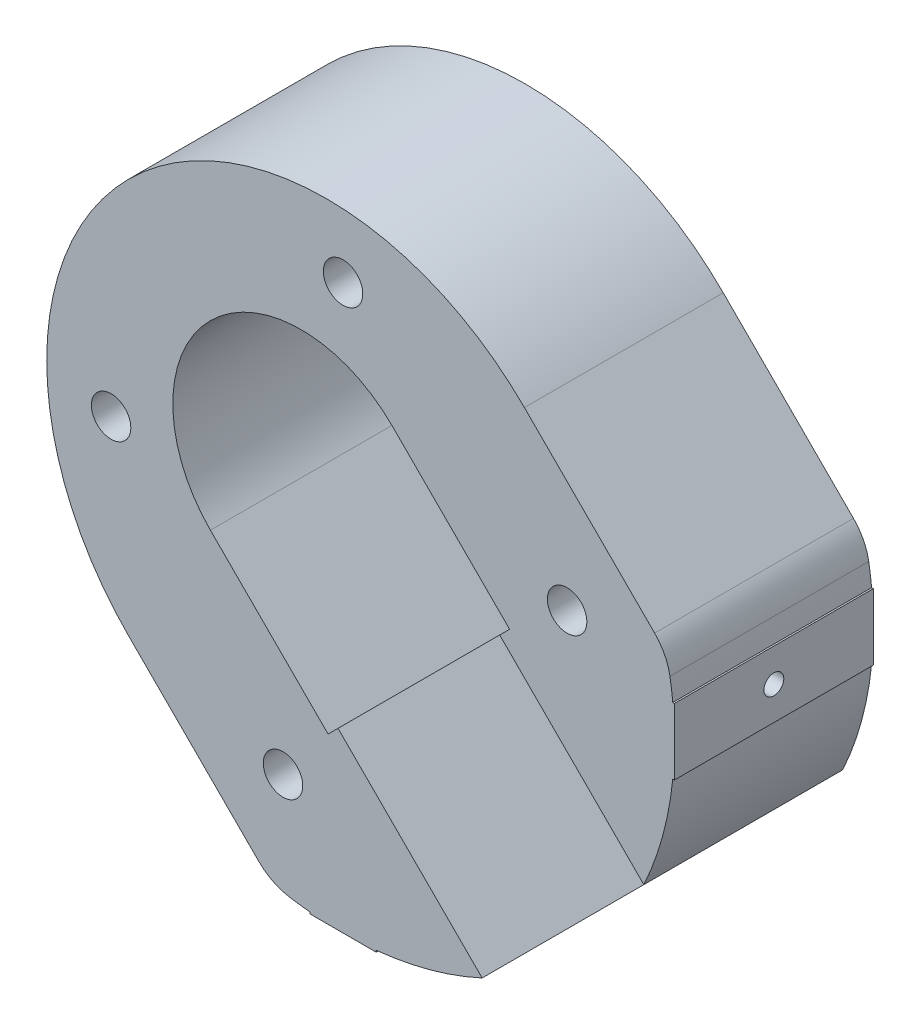
SolidWorks part; units mm, degrees
ref_plane "Front Plane" through (0, 0, 0) normal (0, 0, 1) x (1, 0, 0)
ref_plane "Top Plane" through (0, 0, 0) normal (0, 1, 0) x (1, 0, 0)
ref_plane "Right Plane" through (0, 0, 0) normal (1, 0, 0) x (0, 0, -1)
ref_axis "Z" through (0, 0, 33.5996) along (0, 0, -1)
ref_axis "X" through (56.0652, 0, 0) along (-1, 0, 0)
ref_axis "Y" through (0, -54.2845, 0) along (0, 1, 0)
sketch "Sketch1" plane through (0, 0, 0) normal (0, 0, 1) x (1, 0, 0)
  line L0 (5, -50) -> (-5, -50)
  line L1 (50, 5) -> (50, -5)
  line L2 (56.0652, 0) -> (-1.1166, 0) construction
  line L3 (0, -54.2845) -> (0, 1.1167) construction
  line L4 (61.712, 0) -> (50, 0) construction
  line L5 (0, -50) -> (0, -57.4075) construction
  line L6 (50, -5) -> (49.7494, -5)
  line L7 (5, -49.7494) -> (5, -50)
  line L10 (65.572, -65.572) -> (0, 0) construction
  line L20 (-5, -50) -> (-5, -49.7494)
  line L21 (49.7494, 5) -> (50, 5)
  line L22 (20.987, -45.3822) -> (-0.7634, -23.6318)
  line L23 (45.3822, -20.987) -> (23.6318, 0.7634)
  line L25 (-0.7634, -23.6318) -> (-2.2604, -25.1287)
  line L26 (-2.2604, -25.1287) -> (-20.0175, -7.3715)
  line L27 (23.6318, 0.7634) -> (25.1287, 2.2604)
  line L28 (25.1287, 2.2604) -> (7.3715, 20.0175)
  line L29 (-12.6985, -47.012) -> (-32.3444, -27.3661)
  line L30 (47.012, 12.6985) -> (27.3661, 32.3444)
  circle A0 centre (0, 0) radius 50 construction
  circle A1 centre (0, 0) radius 3.535 construction
  arc A2 (49.7494, -5) -> (5, -49.7494) centre (0, 0) cw construction
  arc A6 (49.7494, 5) -> (49.3214, 8.2098) centre (0, 0) ccw
  arc A7 (5, -49.7494) -> (20.987, -45.3822) centre (0, 0) ccw
  arc A8 (49.7494, -5) -> (45.3822, -20.987) centre (0, 0) cw
  arc A9 (7.3715, 20.0175) -> (-20.0175, -7.3715) centre (-6.323, 6.323) ccw
  arc A10 (-8.2098, -49.3214) -> (-12.6985, -47.012) centre (-6.8523, -41.1658) cw
  arc A12 (-8.2098, -49.3214) -> (-5, -49.7494) centre (0, 0) ccw
  arc A13 (35.3553, -35.3553) -> (-8.2098, -49.3214) centre (0, 0) ccw construction
  arc A15 (49.3214, 8.2098) -> (47.012, 12.6985) centre (41.1658, 6.8523) ccw
  arc A17 (49.3214, 8.2098) -> (35.3553, -35.3553) centre (0, 0) ccw construction
  arc A18 (27.3661, 32.3444) -> (-32.3444, -27.3661) centre (-2.4891, 2.4891) ccw
  dimension "D1" = 100
  dimension "D2" = 7.07
  dimension "D3" = 10
  dimension "D4" = 45
  dimension "D5" = 34.5
extrude "Boss-Extrude1" add sketch "Sketch1" against normal blind 15 and the other way blind 15
sketch "Sketch2" plane through (0, -50, 0) normal (0, 1, 0) x (1, 0, 0)
  line L0 (-57.5886, 0) -> (57.5886, 0) construction
  line L1 (0, -20.5521) -> (0, 20.5521) construction
  circle A0 centre (0, 0) radius 1.5
  dimension "D1" = 3
extrude "Cut-Extrude1" cut sketch "Sketch2" along normal blind 24
sketch "Sketch3" plane through (50, 0, 0) normal (1, 0, 0) x (0, 0, -1)
  circle A0 centre (0, 0) radius 1.5
  dimension "D1" = 3
extrude "Cut-Extrude2" cut sketch "Sketch3" against normal blind 24
sketch "Sketch5" plane through (0, 0, 0) normal (0, 0, 1) x (1, 0, 0)
  line L0 (0, 0) -> (0, -66.8046) construction
  dimension "D1" = 66.8046
ref_plane "Vert" through (0, 0, 0) normal (0.7071, 0.7071, 0) x (0, 0, -1)
sketch "Sketch6" plane through (0, 0, 0) normal (0, 0, 1) x (1, 0, 0)
  line L0 (0, 0) -> (-9.0587, -33.8074) construction
  line L1 (0, 0) -> (18.8244, -18.8244) construction
  line L2 (0, -54.2845) -> (0, 1.1167) construction
  line L3 (0, 0) -> (-35, 0) construction
  circle A0 centre (-9.0587, -33.8074) radius 2.9766
  circle A1 centre (-35, 0) radius 2.9766
  circle A2 centre (0, 35) radius 2.9766
  circle A3 centre (33.8074, 9.0587) radius 2.9766
  dimension "D4" = 5.9531
  dimension "D1" = 35
  dimension "D2" = 45
  dimension "D3" = 60
extrude "Cut-Extrude4" cut sketch "Sketch6" along normal through all
equation "\"EyeDiameter\" = 99.60916292"
equation "\"BasePlaneDistance\" = \"EyeDiameter\"/2+\"L2Thickness\"+\"EyeClearance\""
equation "\"EyeClearance\" = 2"
equation "\"EyeOD\"= \"EyeDiameter\""
equation "\"D2@Sketch1\"= 7.07"
equation "\"pinHoleDiameter\"= 3"
equation "\"D1@Sketch2\"=\"pinHoleDiameter\""
equation "\"D1@Sketch3\"=\"pinHoleDiameter\""
equation "\"D1@Sketch5\"=\"BasePlaneDistance\""
equation "\"L2_ID\" = 20"
equation "\"vx\" = 0"
equation "\"vy\" = 0"
equation "\"vz\" = 200"
equation "\"parametric_end\" = 1"
equation "\"Rw_3_xx\" = -(\"vz\")/sqr((\"vx\")^2 + (\"vz\")^2)"
equation "\"Rw_3_xy\" = 0"
equation "\"Rw_3_xz\" = (\"vx\")/sqr((\"vx\")^2 + (\"vz\")^2)"
equation "\"Rw_3_zx\" = (\"vx\")/sqr((\"vx\")^2 + (\"vy\")^2 + (\"vz\")^2)"
equation "\"Rw_3_zy\" = (\"vy\")/sqr((\"vx\")^2 + (\"vy\")^2 + (\"vz\")^2)"
equation "\"Rw_3_zz\" = (\"vz\")/sqr((\"vx\")^2 + (\"vy\")^2 + (\"vz\")^2)"
equation "\"Rw_3_yx\" = (\"vx\")*(\"vy\")/sqr((\"vx\")^4 + (\"vx\")^2*(\"vy\")^2 + 2*(\"vx\")^2*(\"vz\")^2 + (\"vy\")^2*(\"vz\")^2 + (\"vz\")^4)"
equation "\"Rw_3_yy\" = -sqr((\"vx\")^2 + (\"vz\")^2)/sqr((\"vx\")^2 + (\"vy\")^2 + (\"vz\")^2)"
equation "\"Rw_3_yz\" = (\"vy\")*(\"vz\")/sqr((\"vx\")^4 + (\"vx\")^2*(\"vy\")^2 + 2*(\"vx\")^2*(\"vz\")^2 + (\"vy\")^2*(\"vz\")^2 + (\"vz\")^4)"
equation "\"O2Targx\" = -\"BasePlaneDistance\"*(\"vx\")*(\"vy\")/sqr((\"vx\")^4 + (\"vx\")^2*(\"vy\")^2 + 2*(\"vx\")^2*(\"vz\")^2 + (\"vy\")^2*(\"vz\")^2 + (\"vz\")^4)"
equation "\"O2Targy\" = \"BasePlaneDistance\"*sqr((\"vx\")^2 + (\"vz\")^2)/sqr((\"vx\")^2 + (\"vy\")^2 + (\"vz\")^2)"
equation "\"O2Targz\" = -\"BasePlaneDistance\"*(\"vy\")*(\"vz\")/sqr((\"vx\")^4 + (\"vx\")^2*(\"vy\")^2 + 2*(\"vx\")^2*(\"vz\")^2 + (\"vy\")^2*(\"vz\")^2 + (\"vz\")^4)"
equation "\"O2Targx_0\" = -(\"BasePlaneDistance\")*sqr((\"vx\")^2 + (\"vz\")^2)/sqr((\"vx\")^2 + (\"vy\")^2 + (\"vz\")^2)"
equation "\"O2Targy_0\" = -(\"BasePlaneDistance\")*(\"vy\")*(\"vz\")/sqr((\"vx\")^4 + (\"vx\")^2*(\"vy\")^2 + 2*(\"vx\")^2*(\"vz\")^2 + (\"vy\")^2*(\"vz\")^2 + (\"vz\")^4)"
equation "\"O2Targz_0\" = (\"BasePlaneDistance\")*(\"vx\")*(\"vy\")/sqr((\"vx\")^4 + (\"vx\")^2*(\"vy\")^2 + 2*(\"vx\")^2*(\"vz\")^2 + (\"vy\")^2*(\"vz\")^2 + (\"vz\")^4) + (\"BasePlaneDistance\")"
equation "\"theta2_s1\" = arcsin(((\"BasePlaneDistance\") - (\"O2Targz_0\"))/(\"BasePlaneDistance\")) + pi"
equation "\"theta2_s2\" = -arcsin(((\"BasePlaneDistance\") - (\"O2Targz_0\"))/(\"BasePlaneDistance\"))"
equation "\"theta1_s1\" = arcsin((\"O2Targy_0\")/((\"BasePlaneDistance\")*cos((\"Theta2\")))) + pi"
equation "\"theta1_s2\" = -arcsin((\"O2Targy_0\")/((\"BasePlaneDistance\")*cos((\"Theta2\"))))"
equation "\"theta1_s3\" = -arccos(-(\"O2Targx_0\")/((\"BasePlaneDistance\")*cos((\"Theta2\")))) + 2*pi"
equation "\"theta1_s4\" = arccos(-(\"O2Targx_0\")/((\"BasePlaneDistance\")*cos((\"Theta2\"))))"
equation "\"Theta1\" = \"theta1_s2\" 'so far, theta1_s1 and theta1_s4 have agreed, and they agree with the sw constraint solver"
equation "\"Theta2\" = \"theta2_s2\""
equation "\"o2_x\" = -(\"BasePlaneDistance\")*cos((\"Theta1\"))*cos((\"Theta2\"))"
equation "\"o2_y\" = -(\"BasePlaneDistance\")*sin((\"Theta1\"))*cos((\"Theta2\"))"
equation "\"o2_z\" = (\"BasePlaneDistance\")*(sin((\"Theta2\")) + 1)"
equation "\"o1_x\" = (\"BasePlaneDistance\")*sin((\"Theta1\"))"
equation "\"o1_y\" = -(\"BasePlaneDistance\")*cos((\"Theta1\"))"
equation "\"o1_z\" = (\"BasePlaneDistance\")"
equation "\"Actuator1_Theta\" = atn(\"vx\"/\"vz\") 'ik solution for the single link joint"
equation "\"Actuator2_Theta\" = \"Theta1\"  'ik solution for the double link joint"
equation "\"MotorBaseThickness\" = 3 "
equation "\"BaseThickness\" = 3 "
equation "\"EncoderToMagnetAirgap\" = 1 'Encoder to magnet airgap"
equation "\"EncoderHeight\" = 1.192  'Height of the encoder"
equation "\"MagnetThickness\" = 0.5  'Magnet thickness"
equation "\"pcb_thickness\" = 1.6  'Thickness of the PCB"
equation "\"pcb_outer_diameter\" = 32 'the OD of the pcb"
equation "\"shaft_diameter\" = 4"
equation "\"L2Thickness\" = 3.75 * \"shaft_diameter\""
equation "\"D1@Cut-Extrude2\"=\"shaft_diameter\"*6"
equation "\"D1@Cut-Extrude1\"=\"shaft_diameter\"*6"
